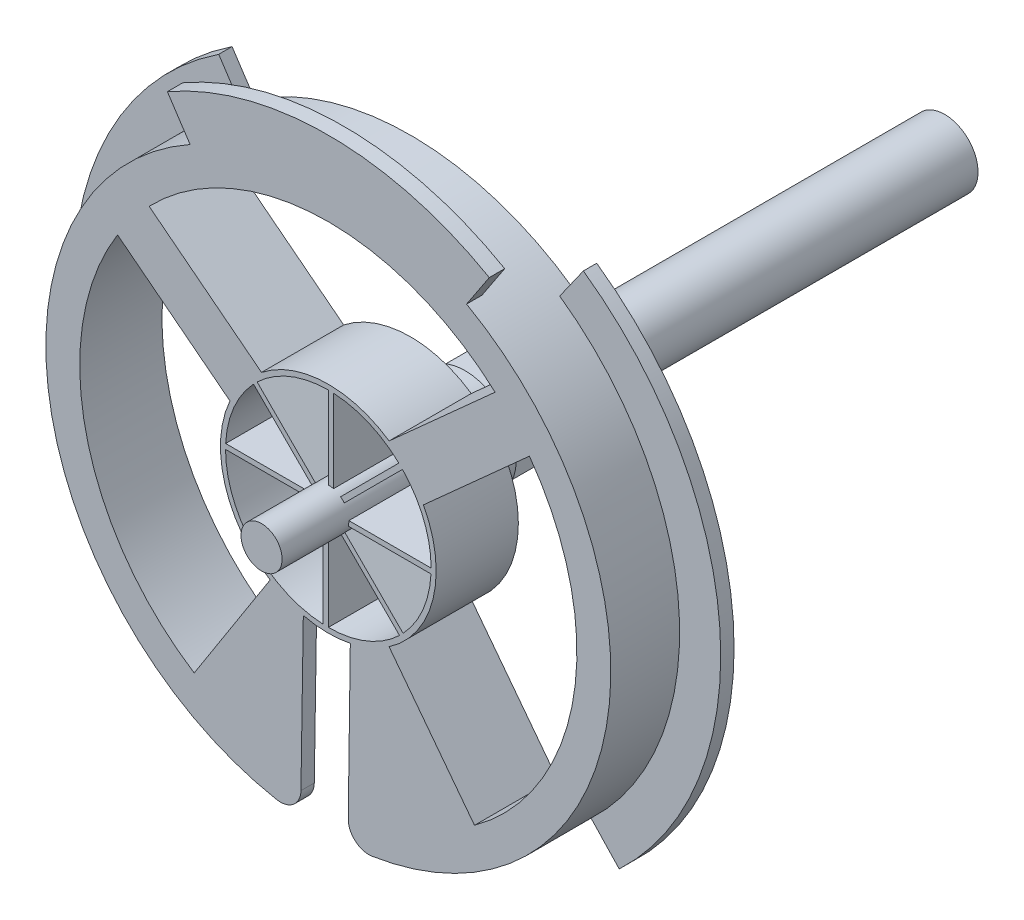
SolidWorks part; units mm, degrees
ref_plane "Alzado" through (0, 0, 0) normal (0, 0, 1) x (1, 0, 0)
ref_plane "Planta" through (0, 0, 0) normal (0, 1, 0) x (1, 0, 0)
ref_plane "Vista lateral" through (0, 0, 0) normal (1, 0, 0) x (0, 0, -1)
sketch "Croquis1" plane through (0, 0, 0) normal (0, 0, 1) x (1, 0, 0)
  circle A0 centre (0, 0) radius 31.5
  dimension "D1" = 63
extrude "Saliente-Extruir1" add sketch "Croquis1" along normal blind 8
sketch "Croquis2" plane through (0, 0, 8) normal (0, 0, 1) x (1, 0, 0)
  circle A0 centre (0, 0) radius 31.5
  circle A1 centre (0, 0) radius 27.5
  dimension "D1" = 4
  dimension "D2" = 63
extrude "Cortar-Extruir2" cut sketch "Croquis2" against normal blind 6.7
sketch "Croquis3" plane through (0, 0, 8) normal (0, 0, 1) x (1, 0, 0)
  line L1 (-28.7567, 23.3642) -> (-23.7972, 19.42) construction
  line L2 (-23.1338, 14.8687) -> (-20.0592, 18.8117)
  line L3 (-23.1338, 14.8687) -> (-9.1728, 3.9824)
  line L4 (-20.0592, 18.8117) -> (-6.0982, 7.9254)
  line L7 (18.7038, 20.1599) -> (5.5329, 8.3299)
  line L8 (22.0449, 16.44) -> (8.874, 4.6101)
  line L11 (14.9496, 16.7879) -> (18.7038, 20.1599)
  line L12 (18.2907, 13.0681) -> (22.0449, 16.44)
  line L14 (-18.7228, 11.4292) -> (-23.1338, 14.8687)
  line L15 (-15.6482, 15.3721) -> (-20.0592, 18.8117)
  line L17 (-21.2803, 17.4184) -> (-7.5799, 6.5227) construction
  line L18 (-14.8379, -23.1535) -> (-5.6654, -8.8404)
  line L19 (-5.6654, -8.8404) -> (-4.6998, -8.8268)
  line L20 (5.9135, -8.6764) -> (16.2319, -22.1986)
  line L21 (0, 0) -> (0, -2.5) construction
  line L23 (-2.7019, -27.3669) -> (-2.4355, -10.2136)
  line L24 (1.9086, -27.4337) -> (2.1388, -10.2799)
  line L25 (-0.1448, -9.999) -> (0, -10.001)
  line L26 (4.9479, -8.6901) -> (5.9135, -8.6764)
  line L27 (0, -8.7602) -> (0, -10.5) construction
  circle A0 centre (0, 0) radius 10
  circle A1 centre (0, 0) radius 2.5
  circle A2 centre (0, 0) radius 27.5 construction
  circle A3 centre (0, 0) radius 27.5 construction
  arc A4 (-20.0592, 18.8117) -> (-23.1338, 14.8687) centre (0, 0) ccw
  circle A5 centre (0, 0) radius 10
  circle A6 centre (0, 0) radius 10.5
  arc A7 (1.9086, -27.4337) -> (16.2319, -22.1986) centre (0, 0) ccw
  arc A8 (-14.8379, -23.1535) -> (16.2319, -22.1986) centre (0, 0) ccw
  arc A9 (-14.8379, -23.1535) -> (-2.7019, -27.3669) centre (0, 0) ccw
  arc A10 (-20.0592, 18.8117) -> (-23.1338, 14.8687) centre (0, 0) ccw
  arc A11 (22.0449, 16.44) -> (18.7038, 20.1599) centre (0, 0) ccw
  arc A13 (22.0449, 16.44) -> (18.7038, 20.1599) centre (0, 0) ccw
  circle A14 centre (0, 0) radius 24.2
  circle M22 centre (0, 0) radius 27.5
  dimension "D1" = 20
  dimension "D2" = 5
  dimension "D6" = 21
  dimension "D10" = 3.3
  dimension "D3" = 5
  dimension "D4" = 5
  dimension "D5" = 70
  dimension "D7" = 13.961
  dimension "D8" = 13.1709
  dimension "D9" = 2.5
extrude "Cortar-Extruir4" cut sketch "Croquis3" against normal through all contours L11 A14 L15 L4 A6 L7 | L14 A14 L18 A6 L3 | L20 A14 L12 L8 A6 region at (-16.1393, -3.9115, 8) region at (-0.584, 16.7928, 8) region at (16.2874, -2.9215, 8)
extrude "Cortar-Extruir5" cut sketch "Croquis3<4>" against normal through all contours L23 A14 L24 A6 | A14 L23 L24 M22 region at (-0.3737, -25.8133, 8) region at (-0.2504, -17.2952, 8)
sketch "Croquis3<4>" plane through (0, 0, 8) normal (0, 0, 1) x (1, 0, 0) same geometry as "Croquis3"
sketch "Croquis4" plane through (0, 0, 1.3) normal (0, 0, 1) x (1, 0, 0)
  line L0 (-2.7019, -27.3669) -> (1.9086, -27.4337)
  line L1 (-2.7019, -27.3669) -> (-2.7922, -33.5998)
  line L2 (1.9086, -27.4337) -> (1.8184, -33.6665)
  line L3 (-2.7922, -33.5998) -> (1.8184, -33.6665)
extrude "Cortar-Extruir6" cut sketch "Croquis4" against normal through all
sketch "Croquis5" plane through (0, 0, 1.3) normal (0, 0, 1) x (1, 0, 0)
  line L0 (15.8246, 22.4907) -> (18.1264, 25.7621)
  line L1 (18.1264, 25.7621) -> (15.8246, 22.4907)
  line L2 (0, 0) -> (0.456, 31.4967) construction
  line L3 (-17.373, 26.276) -> (-15.1669, 22.9394)
  line L4 (-19.4454, -19.4454) -> (-22.2739, -22.2739)
  line L5 (-22.2739, -22.2739) -> (-19.4454, -19.4454)
  line L6 (21.6198, -22.9093) -> (18.8744, -20.0002)
  arc A0 (1.9086, -27.4337) -> (-2.7019, -27.3669) centre (0, 0) ccw construction
  arc A1 (1.8505, -31.4456) -> (-2.76, -31.3789) centre (0, 0) ccw construction
  arc A2 (21.6198, -22.9093) -> (18.1264, 25.7621) centre (0, 0) ccw
  arc A3 (1.9086, -27.4337) -> (-2.7019, -27.3669) centre (0, 0) ccw construction
  arc A4 (1.9086, -27.4337) -> (-2.7019, -27.3669) centre (0, 0) ccw
  arc A5 (-17.373, 26.276) -> (-22.2739, -22.2739) centre (0, 0) ccw
  line M4 (-2.76, -31.3789) -> (-2.7019, -27.3669)
  arc M5 (-2.7019, -27.3669) -> (1.9086, -27.4337) centre (0, 0) cw
  line M6 (1.9086, -27.4337) -> (1.8505, -31.4456)
  arc M7 (1.8505, -31.4456) -> (-2.76, -31.3789) centre (0, 0) ccw
extrude "Cortar-Extruir7" cut sketch "Croquis5" against normal through all contours L2 L3 M5 M7 | L2 A4 L0 M7 | L6 M7 M5 M6 | L4 M5 M7 M4 region at (8.9845, 27.6846, 1.3) region at (11.5458, -26.562, 1.3) region at (-8.1794, 27.933, 1.3) region at (-12.3099, -26.2166, 1.3)
sketch "Croquis6" plane through (0, 0, 0) normal (0, 0, -1) x (-1, 0, 0)
  line L0 (-4.2936, -9.582) -> (-14.7113, -23.2342)
  line L1 (3.8714, -9.7602) -> (13.1088, -24.1746)
  line L2 (-5.9135, -8.6764) -> (-14.2295, -19.5745) construction
  line L3 (13.0574, -20.3751) -> (5.6654, -8.8404) construction
  arc A0 (-14.7113, -23.2342) -> (13.1088, -24.1746) centre (0, 0) ccw
  arc A1 (-4.2936, -9.582) -> (3.8714, -9.7602) centre (0, 0) ccw
extrude "Cortar-Extruir8" cut sketch "Croquis6" against normal blind 6.7
fillet "Redondeo1" radius 2 2 edges at (1.9086, -27.4337, 7.35) (-2.7019, -27.3669, 7.35)
sketch "Croquis7" plane through (0, 0, 8) normal (0, 0, 1) x (1, 0, 0)
  line L0 (0, 0) -> (0, 19.7684) construction
  line L1 (-15.6697, 27.326) -> (-13.4585, 23.9817)
  line L2 (-17.373, 26.276) -> (-15.1669, 22.9394) construction
  line L3 (15.6697, 27.326) -> (13.4585, 23.9817)
  arc A0 (15.6697, 27.326) -> (-15.6697, 27.326) centre (0, 0) ccw
  arc A2 (4.2478, -27.17) -> (-5.0325, -27.0356) centre (0, 0) ccw construction
  arc A3 (13.4585, 23.9817) -> (-13.4585, 23.9817) centre (0, 0) ccw
  dimension "D2" = 31.5
  dimension "D1" = 2
extrude "Saliente-Extruir2" add sketch "Croquis7" against normal blind 1.5
sketch "Croquis8" plane through (0, 0, 8) normal (0, 0, 1) x (1, 0, 0)
  line L0 (0, 2) -> (0, 10.0074)
  line L1 (-1.2604, 1.5529) -> (-6.9286, 7.221)
  line L2 (0.5, 1.9365) -> (0.5, 9.9949)
  line L3 (-7.2806, 6.8659) -> (-1.6063, 1.1916)
  line L4 (2, 0) -> (10.0074, 0)
  line L5 (1.5529, 1.2604) -> (7.221, 6.9286)
  line L6 (1.9365, -0.5) -> (9.9949, -0.5)
  line L7 (6.8659, 7.2806) -> (1.1916, 1.6063)
  line L8 (0, -2) -> (0, -10.0074)
  line L9 (1.2604, -1.5529) -> (6.9286, -7.221)
  line L10 (-0.5, -1.9365) -> (-0.5, -9.9949)
  line L11 (7.2806, -6.8659) -> (1.6063, -1.1916)
  line L12 (-2, 0) -> (-10.0074, 0)
  line L13 (-1.5529, -1.2604) -> (-7.221, -6.9286)
  line L14 (-1.9365, 0.5) -> (-9.9949, 0.5)
  line L15 (-6.8659, -7.2806) -> (-1.1916, -1.6063)
  circle A0 centre (0, 0) radius 2
  arc A1 (10.0074, 0) -> (7.221, 6.9286) centre (0, 0) ccw
  arc A3 (0, 10.0074) -> (-6.9286, 7.221) centre (0, 0) ccw
  arc A4 (0, -10.0074) -> (6.9286, -7.221) centre (0, 0) ccw
  arc A5 (-10.0074, 0) -> (-7.221, -6.9286) centre (0, 0) ccw
  arc A6 (0, 10.0074) -> (-6.9286, 7.221) centre (0, 0) ccw
  circle A7 centre (0, 0) radius 10.5
  arc A8 (6.8659, 7.2806) -> (0.5, 9.9949) centre (0, 0) ccw
  arc A9 (10.0074, 0) -> (7.221, 6.9286) centre (0, 0) ccw
  arc A10 (7.2806, -6.8659) -> (9.9949, -0.5) centre (0, 0) ccw
  arc A11 (0, -10.0074) -> (6.9286, -7.221) centre (0, 0) ccw
  arc A12 (-6.8659, -7.2806) -> (-0.5, -9.9949) centre (0, 0) ccw
  arc A13 (-10.0074, 0) -> (-7.221, -6.9286) centre (0, 0) ccw
  arc A14 (-7.2806, 6.8659) -> (-9.9949, 0.5) centre (0, 0) ccw
  point P6 (0, 0)
  point P40 (0, 0)
  dimension "D1" = 4
  dimension "D5" = 0.2068
  dimension "D6" = 10.0074
  dimension "D8" = 21
  dimension "D2" = 45
  dimension "D3" = 0.5
  dimension "D4" = 0.5
  dimension "D7" = 4
extrude "Cortar-Extruir9" cut sketch "Croquis8" against normal blind 7 and the other way through all contours L7 A8 L2 A0 | L0 A3 L1 A0 | L4 A1 L5 A0 | L11 A10 L6 A0 | L8 A4 L9 A0 | L15 A12 L10 A0 | L12 A5 L13 A0 | L3 A14 L14 A0 region at (-2.4974, 6.2932, 8) region at (2.75, 6.3733, 8) region at (-6.3733, 2.75, 8) region at (6.2932, 2.4974, 8) region at (-6.2932, -2.4974, 8) region at (6.3733, -2.75, 8) region at (-2.75, -6.3733, 8) region at (2.4974, -6.2932, 8)
sketch "Croquis9" plane through (0, 0, 8) normal (0, 0, 1) x (1, 0, 0)
  circle A0 centre (0, 0) radius 2
extrude "Saliente-Extruir3" add sketch "Croquis9" along normal blind 6.5
sketch "Croquis10" plane through (0, 0, 0) normal (0, 0, -1) x (-1, 0, 0)
  line L1 (3.25, -3.25) -> (-3.25, -3.25)
  line L2 (3.25, -3.25) -> (3.25, 3.25)
  line L3 (3.25, 3.25) -> (-3.25, 3.25)
  line L4 (-3.25, -3.25) -> (-3.25, 3.25)
  line L5 (3.25, -3.25) -> (-3.25, 3.25) construction
  line L6 (3.25, 3.25) -> (-3.25, -3.25) construction
  circle A0 centre (0, 0) radius 5
  dimension "D1" = 10
  dimension "D2" = 6.5
  dimension "D3" = 6.5
extrude "Saliente-Extruir5" add sketch "Croquis10" along normal blind 5.3
extrude "Saliente-Extruir6" add sketch "Croquis10<3>" along normal blind 15 contours L4 L1 L2 L3 region at (0, 0, 0)
sketch "Croquis10<3>" plane through (0, 0, 0) normal (0, 0, -1) x (-1, 0, 0) same geometry as "Croquis10"
sketch "Croquis11" plane through (0, 0, -15) normal (0, 0, -1) x (-1, 0, 0)
  circle A0 centre (0, 0) radius 3.25
extrude "Saliente-Extruir7" add sketch "Croquis11" along normal blind 37
